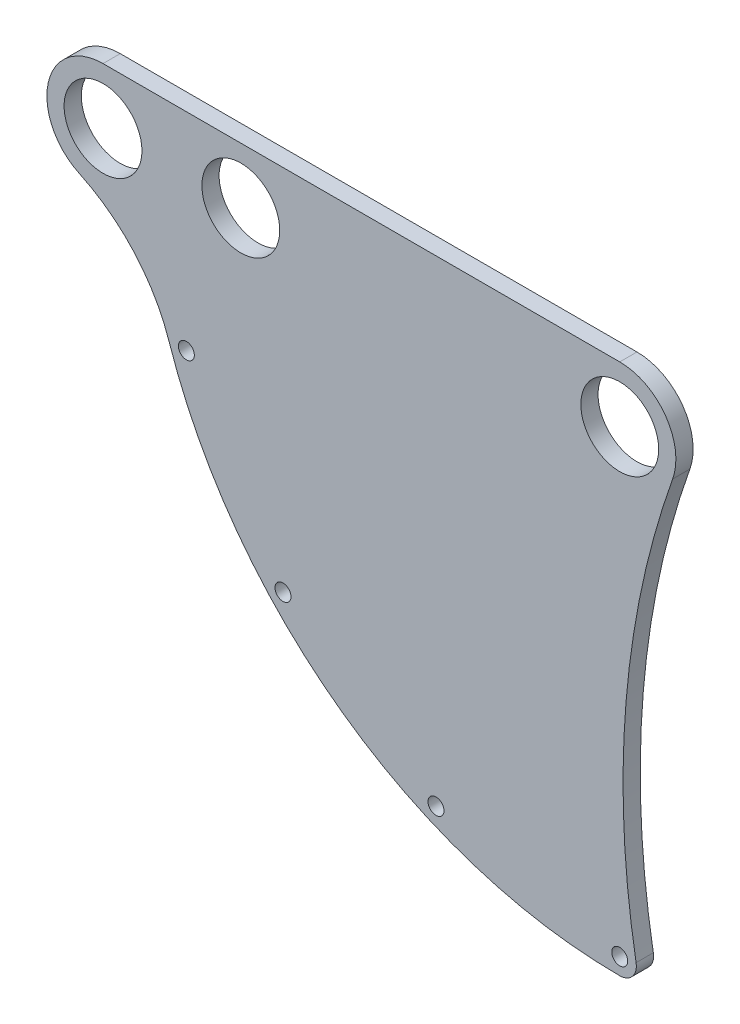
SolidWorks part; units mm, degrees
material "6061-T6 (SS)"
ref_plane "Front Plane" through (0, 0, 0) normal (0, 0, 1) x (1, 0, 0)
ref_plane "Top Plane" through (0, 0, 0) normal (0, 1, 0) x (1, 0, 0)
ref_plane "Right Plane" through (0, 0, 0) normal (1, 0, 0) x (0, 0, -1)
sketch "Sketch1" plane through (0, 0, 0) normal (0, 0, 1) x (1, 0, 0)
  line L1 (0, 0) -> (422.275, 0) construction
  line L2 (0, 0) -> (0, 250.825) construction
  line L3 (0, 250.825) -> (422.275, 250.825) construction
  line L4 (422.275, 0) -> (422.275, 250.825) construction
  line L5 (129.8504, 75.2912) -> (186.2558, 35.1899) construction
  line L6 (186.2558, 35.1899) -> (254, 21.033) construction
  line L7 (342.9, 250.825) -> (342.9, 0) construction
  line L8 (382.5875, 27.383) -> (382.5875, 190.197) construction
  line L10 (422.275, 27.383) -> (382.5875, 27.383) construction
  line L11 (0, 225.425) -> (0, 0)
  line L13 (254, 21.033) -> (129.8504, 75.2912) construction
  line L14 (250.3338, 27.383) -> (246.6677, 21.033) construction
  line L15 (246.6677, 21.033) -> (250.3338, 14.683) construction
  line L16 (250.3338, 14.683) -> (257.6662, 14.683) construction
  line L17 (257.6662, 14.683) -> (261.3323, 21.033) construction
  line L18 (261.3323, 21.033) -> (257.6662, 27.383) construction
  line L19 (257.6662, 27.383) -> (250.3338, 27.383) construction
  line L20 (185.4394, 42.4767) -> (179.5371, 38.1263) construction
  line L21 (179.5371, 38.1263) -> (180.3535, 30.8395) construction
  line L22 (180.3535, 30.8395) -> (187.0723, 27.9032) construction
  line L23 (187.0723, 27.9032) -> (192.9746, 32.2536) construction
  line L24 (192.9746, 32.2536) -> (192.1582, 39.5404) construction
  line L25 (192.1582, 39.5404) -> (185.4394, 42.4767) construction
  line L26 (132.0204, 82.2951) -> (124.8698, 80.6725) construction
  line L27 (124.8698, 80.6725) -> (122.6998, 73.6686) construction
  line L28 (122.6998, 73.6686) -> (127.6804, 68.2874) construction
  line L29 (127.6804, 68.2874) -> (134.8309, 69.91) construction
  line L30 (134.8309, 69.91) -> (137.0009, 76.9139) construction
  line L31 (137.0009, 76.9139) -> (132.0204, 82.2951) construction
  line L32 (91.186, 186.5308) -> (91.186, 193.8632) construction
  line L33 (91.186, 193.8632) -> (84.836, 197.5293) construction
  line L34 (84.836, 197.5293) -> (78.486, 193.8632) construction
  line L35 (78.486, 193.8632) -> (78.486, 186.5308) construction
  line L36 (78.486, 186.5308) -> (84.836, 182.8647) construction
  line L37 (84.836, 182.8647) -> (91.186, 186.5308) construction
  line L38 (186.2558, 35.1899) -> (94.2245, 134.6249) construction
  line L39 (186.2558, 35.1899) -> (191.9252, 48.1621) construction
  line L40 (129.8504, 75.2912) -> (140.2402, 84.9074) construction
  line L41 (129.8504, 75.2912) -> (85.3411, 203.26) construction
  line L42 (89.4313, 129.0762) -> (96.6333, 127.6995) construction
  line L43 (96.6333, 127.6995) -> (101.4265, 133.2483) construction
  line L44 (101.4265, 133.2483) -> (99.0177, 140.1737) construction
  line L45 (99.0177, 140.1737) -> (91.8158, 141.5503) construction
  line L46 (91.8158, 141.5503) -> (87.0226, 136.0016) construction
  line L47 (87.0226, 136.0016) -> (89.4313, 129.0762) construction
  line L48 (107.5958, 139.2756) -> (94.2245, 134.6249) construction
  line L49 (0, 225.425) -> (342.9, 225.425)
  line L50 (342.9, 225.425) -> (342.9, 0)
  line L51 (342.9, 0) -> (0, 0)
  line L52 (63.5, 190.197) -> (254, 190.197) construction
  circle A0 centre (254, 190.197) radius 14.351
  circle A1 centre (254, 21.033) radius 2.9464
  circle A2 centre (186.2558, 35.1899) radius 2.9464
  circle A3 centre (129.8504, 75.2912) radius 2.9464
  circle A4 centre (84.836, 190.197) radius 2.9464 construction
  arc A5 (254, 21.033) -> (84.836, 190.197) centre (254, 190.197) cw construction
  circle A10 centre (254, 190.197) radius 38.1 construction
  circle A12 centre (382.5875, 190.197) radius 38.1 construction
  circle A13 centre (254, 21.033) radius 6.35 construction
  circle A14 centre (186.2558, 35.1899) radius 6.35 construction
  circle A15 centre (129.8504, 75.2912) radius 6.35 construction
  circle A16 centre (84.836, 190.197) radius 6.35 construction
  circle A17 centre (63.5, 190.197) radius 14.351
  circle A18 centre (63.5, 190.197) radius 38.1 construction
  circle A19 centre (94.2245, 134.6249) radius 6.35 construction
  circle A20 centre (94.2245, 134.6249) radius 2.9464
  circle A21 centre (114.3, 190.197) radius 14.351
  point P21 (158.75, 190.197)
  dimension "D3" = 28.702
  dimension "D4" = 76.2
  dimension "D10" = 76.2
  dimension "D5" = 190.5
  dimension "D14" = 5.8928
  dimension "D15" = 12.7
  dimension "D18" = 50.8
  dimension "D1" = 422.275
  dimension "D2" = 225.425
  dimension "D6" = 158.75
  dimension "D7" = 162.814
  dimension "D8" = 162.814
  dimension "D9" = 223.442
  dimension "D11" = 88.9
  dimension "D12" = 39.6875
  dimension "D13" = 25.4
  dimension "D16" = 63.5
  dimension "D17" = 184.15
extrude "Boss-Extrude1" add sketch "Sketch1" along normal blind 6.35
sketch "Sketch2" plane through (0, 0, 6.35) normal (0, 0, 1) x (1, 0, 0)
  line L4 (63.5, 210.898) -> (254, 210.898)
  line L6 (349.25, 0) -> (0, 0)
  line L7 (342.9, 225.425) -> (0, 225.425) construction
  line L8 (349.25, 0) -> (349.25, 250.825)
  line L9 (0, 250.825) -> (349.25, 250.825)
  line L10 (0, 250.825) -> (0, 0)
  line L13 (349.25, 58.7375) -> (0, 58.7375) construction
  line L14 (342.9, 0) -> (342.9, 225.425) construction
  line L15 (260.0284, 22.096) -> (259.4557, 25.3442) construction
  line L16 (260.0284, 22.096) -> (260.0284, 12.3299) construction
  line L17 (349.25, 109.5375) -> (0, 109.5375) construction
  arc A0 (254, 14.9116) -> (260.0284, 22.096) centre (254, 21.033) ccw
  arc A4 (63.5, 210.898) -> (54.6994, 171.4599) centre (63.5, 190.197) ccw
  arc A5 (273.5063, 183.2663) -> (254, 210.898) centre (254, 190.197) ccw
  circle A7 centre (63.5, 190.197) radius 14.351 construction
  circle A8 centre (254, 21.033) radius 2.9464 construction
  arc A10 (273.5063, 183.2663) -> (260.0284, 22.096) centre (572.1961, 77.1396) ccw
  arc A11 (254, 14.9116) -> (87.8824, 134.2512) centre (254, 190.197) cw
  arc A12 (54.6994, 171.4599) -> (87.8824, 134.2512) centre (27.7037, 113.9839) cw
  dimension "D1" = 3.175
  dimension "D2" = 6.35
  dimension "D3" = 63.5
  dimension "D6" = 10
  dimension "D4" = 25.4
  dimension "D5" = 6.35
  dimension "D7" = 58.7375
  dimension "D8" = 50.8
sketch "Sketch3" plane through (0, 0, 6.35) normal (0, 0, 1) x (1, 0, 0)
  line L0 (63.5, 190.197) -> (254, 190.197) construction
  line L1 (0, 225.425) -> (82.55, 225.425)
  line L2 (0, 225.425) -> (0, 250.825)
  line L3 (0, 250.825) -> (82.55, 250.825)
  line L4 (82.55, 225.425) -> (82.55, 250.825)
  line L5 (342.9, 225.425) -> (234.95, 225.425)
  line L6 (342.9, 225.425) -> (342.9, 250.825)
  line L7 (342.9, 250.825) -> (234.95, 250.825)
  line L8 (234.95, 225.425) -> (234.95, 250.825)
  line L9 (82.55, 225.425) -> (234.95, 225.425) construction
  line L10 (158.75, 225.425) -> (158.75, 190.197) construction
  dimension "D1" = 25.4
  dimension "D2" = 152.4
extrude "Boss-Extrude2" add sketch "Sketch3" against normal up to surface (6.35 mm away) up to face at (171.45, 112.7125, 0)
extrude "Cut-Extrude1" cut sketch "Sketch2" against normal through all
